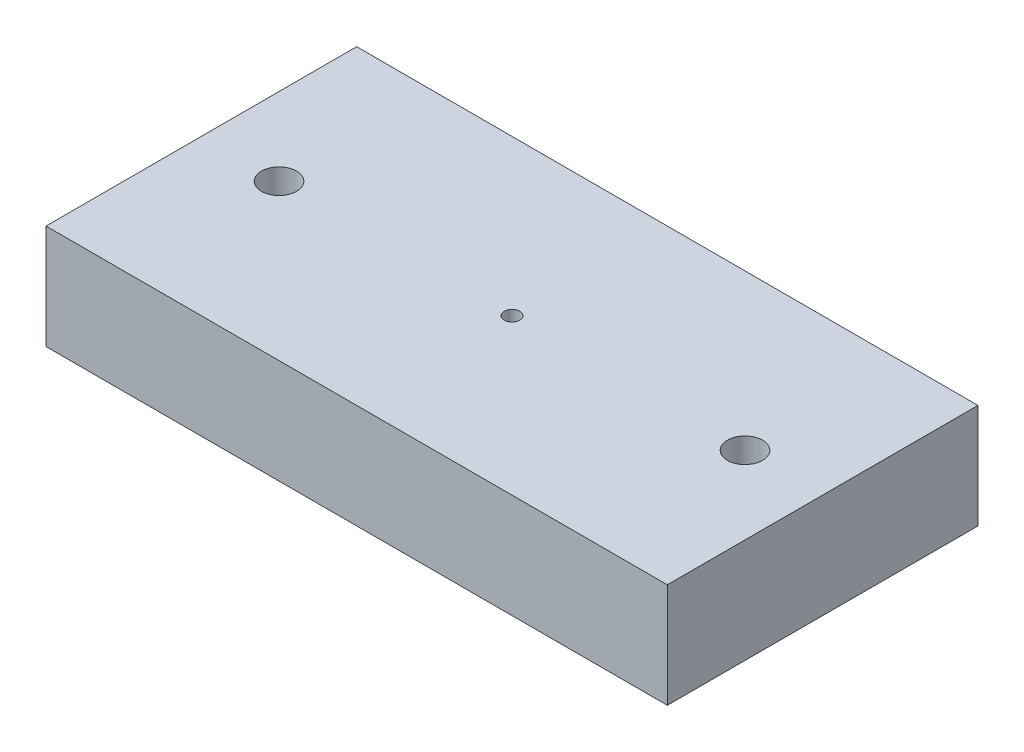
SolidWorks part; units mm, degrees
ref_plane "Front Plane" through (0, 0, 0) normal (0, 0, 1) x (1, 0, 0)
ref_plane "Top Plane" through (0, 0, 0) normal (0, 1, 0) x (1, 0, 0)
ref_plane "Right Plane" through (0, 0, 0) normal (1, 0, 0) x (0, 0, -1)
sketch "Sketch1" plane through (0, 0, 0) normal (0, 1, 0) x (1, 0, 0)
  line L1 (-20, -10) -> (20, -10)
  line L2 (-20, -10) -> (-20, 10)
  line L3 (-20, 10) -> (20, 10)
  line L4 (20, -10) -> (20, 10)
  line L5 (-20, -10) -> (20, 10) construction
  line L6 (-20, 10) -> (20, -10) construction
  point P0 (0, 0)
extrude "Boss-Extrude1" add sketch "Sketch1" along normal blind 6.72
sketch "Sketch2" plane through (0, 6.72, 0) normal (0, 1, 0) x (1, 0, 0)
  circle A0 centre (0, 0) radius 0.5
extrude "Cut-Extrude1" cut sketch "Sketch2" against normal blind 6.72
hole_wizard "#4-40 Tapped Hole1" positions "3DSketch4" profile "Sketch9" tap size "#4-40" standard "ANSI Inch"
sketch3d "3DSketch4"
  point P0 (-15, 0, 0)
sketch "Sketch9" plane through (-15, 0, 0) normal (1, 0, 0) x (0, 0, -1)
  line L0 (0, 0) -> (0, 8.2792)
  line L1 (0, 8.2792) -> (1.1303, 7.6)
  line L2 (1.1303, 7.6) -> (1.1303, 0.635)
  line L3 (1.1303, 0.635) -> (1.7653, 0)
  line L5 (1.7653, 0) -> (0, 0)
  line L6 (-1.1303, 0.635) -> (-1.7653, 0) construction
  line L10 (0, 8.2792) -> (-1.1303, 7.6) construction
  line L11 (0, -6.35) -> (0, 107.95) construction
  dimension "Tap Drill Dia." = 2.2606
  dimension "Tap Drill Depth" = 7.6
  dimension "Near C'Sink Dia." = 3.5306
  dimension "Near C'Sink Angle" = 90
  dimension "Drill Angle" = 118
cosmetic thread "Hole Thread1" parameters "D1"=5.69, "D2"=2.8448
sketch "Sketch11" plane through (0, 0, 0) normal (0, -1, 0) x (1, 0, 0)
  line L0 (-20, 0) -> (20, 0) construction
  line L1 (-20, -10) -> (-20, 10) construction
  line L2 (20, 10) -> (20, -10) construction
pattern_linear "LPattern1" count 2 spacing 30 along (1, 0, 0) of "#4-40 Tapped Hole1"
sketch "Sketch12" plane through (0, 0, 0) normal (0, -1, 0) x (1, 0, 0)
  circle A0 centre (0, 0) radius 4
  circle A1 centre (0, 0) radius 5.05
extrude "Cut-Extrude2" cut sketch "Sketch12" against normal blind 4.72
sketch "Sketch13" plane through (0, 0, 0) normal (0, -1, 0) x (1, 0, 0)
  line L1 (-2.5, 1.75) -> (2.5, 1.75)
  line L2 (-2.5, 1.75) -> (-2.5, -1.75)
  line L3 (-2.5, -1.75) -> (2.5, -1.75)
  line L4 (2.5, 1.75) -> (2.5, -1.75)
  line L5 (-2.5, 1.75) -> (2.5, -1.75) construction
  line L6 (-2.5, -1.75) -> (2.5, 1.75) construction
extrude "Cut-Extrude3" cut sketch "Sketch13" against normal blind 0.5
